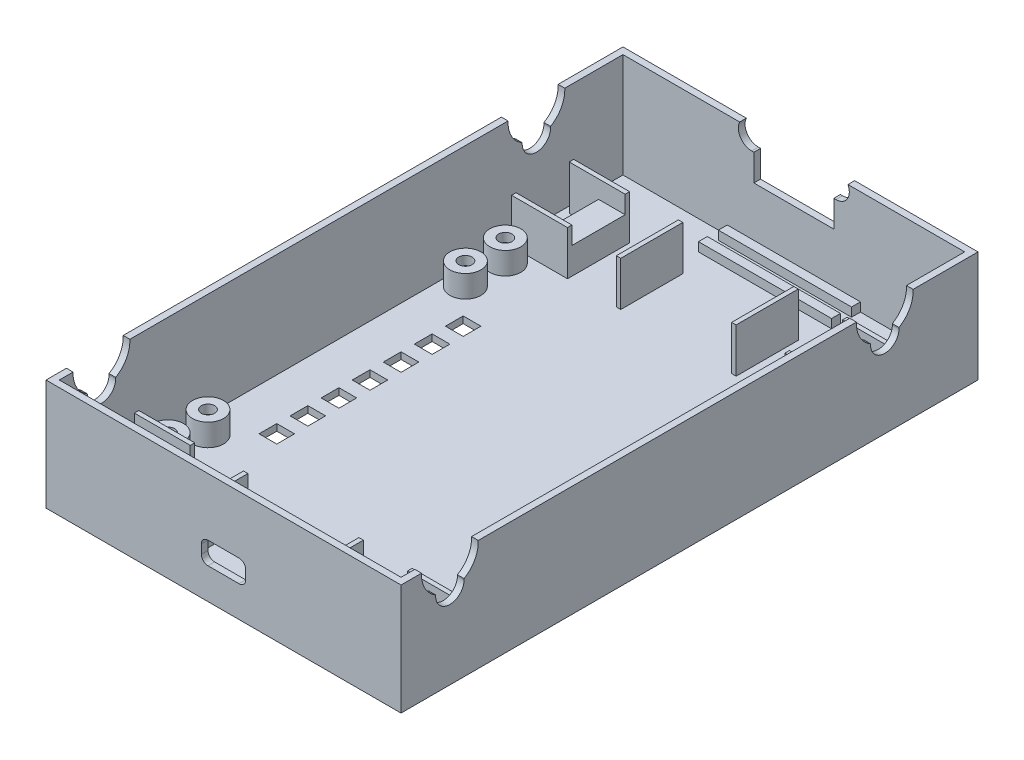
SolidWorks part; units mm, degrees
ref_plane "Спереди" through (0, 0, 0) normal (0, 0, 1) x (1, 0, 0)
ref_plane "Сверху" through (0, 0, 0) normal (0, 1, 0) x (1, 0, 0)
ref_plane "Справа" through (0, 0, 0) normal (1, 0, 0) x (0, 0, -1)
other "Configuration Table"
sketch "Корпус" plane through (0, 0, 0) normal (0, 1, 0) x (1, 0, 0)
  line L1 (40, -65) -> (-40, -65)
  line L2 (40, -65) -> (40, 65)
  line L3 (40, 65) -> (-40, 65)
  line L4 (-40, -65) -> (-40, 65)
  line L5 (40, -65) -> (-40, 65) construction
  line L6 (40, 65) -> (-40, -65) construction
  point P0 (0, 0)
  dimension "D1" = 80
  dimension "D2" = 130
sketch3d "Трехмерный эскиз1" plane through (0, 0, 0) normal (0, 0, 1) x (1, 0, 0)
extrude "Бобышка-Вытянуть1" add sketch "Корпус" along normal blind 25
sketch "Эскиз1" plane through (0, 25, 0) normal (0, 1, 0) x (1, 0, 0)
  line L0 (40, 65) -> (-40, 65) construction
  line L5 (-38.5, 63.5) -> (38.5, 63.5)
  line L6 (-38.5, 63.5) -> (-38.5, -63.5)
  line L7 (-38.5, -63.5) -> (38.5, -63.5)
  line L8 (38.5, 63.5) -> (38.5, -63.5)
  line L9 (-38.5, 63.5) -> (38.5, -63.5) construction
  line L10 (-38.5, -63.5) -> (38.5, 63.5) construction
  line L11 (-40, 65) -> (-40, -65) construction
  point P0 (0, 0)
  dimension "D1" = 1.5
  dimension "D2" = 1.5
extrude "Вырез-Вытянуть1" cut sketch "Эскиз1" against normal offset from surface (23.5 mm away) 1.5 up to face at (0, 0, 0)
sketch "Эскиз2" plane through (0, 0, -63.5) normal (0, 0, 1) x (1, 0, 0)
  line L0 (-14.3, 33.5) -> (14.3, 33.5) construction
  line L5 (-9, 26.7) -> (-9, 32.7)
  line L6 (-9, 32.7) -> (9, 32.7)
  line L7 (14.3, 33.5) -> (14.3, 4.5) construction
  line L8 (14.3, 4.5) -> (-14.3, 4.5) construction
  line L9 (-14.3, 4.5) -> (-14.3, 33.5) construction
  line L10 (0, 33.5) -> (0, 4.5) construction
  line L11 (9, 32.7) -> (9, 26.7)
  line L12 (9, 26.7) -> (9.5, 26.7)
  line L13 (-9, 26.7) -> (-9.5, 26.7)
  line L14 (9.5, 20.7) -> (9, 20.7)
  line L15 (9, 20.7) -> (9, 14.7)
  line L16 (9, 14.7) -> (-9, 14.7)
  line L17 (-9, 14.7) -> (-9, 20.7)
  line L18 (-9, 20.7) -> (-9.5, 20.7)
  line L20 (-12.5, 23.7) -> (12.5, 23.7) construction
  line L21 (-38.5, 1.5) -> (-38.5, 25) construction
  line L22 (38.5, 25) -> (-38.5, 25) construction
  line L23 (-40, 25) -> (40, 25) construction
  line L24 (0, 0) -> (0, 25) construction
  line L25 (-40, 0) -> (40, 0) construction
  arc A4 (-9.5, 26.7) -> (-9.5, 20.7) centre (-9.5, 23.7) ccw
  arc A5 (9.5, 26.7) -> (9.5, 20.7) centre (9.5, 23.7) cw
  point P32 (0, 23.7)
  dimension "D2" = 4.5
  dimension "D3" = 25
  dimension "D4" = 3
  dimension "D5" = 28.6
  dimension "D6" = 28.6
  dimension "D7" = 29
  dimension "D8" = 18
  dimension "D9" = 9.8
  dimension "D10" = 18
  dimension "D11" = 6
  dimension "D12" = 19.2
extrude "Вырез-Вытянуть2" cut sketch "Эскиз2" against normal blind 2
sketch "Эскиз3" plane through (-40, 0, 0) normal (-1, 0, 0) x (0, 0, 1)
  line L1 (-50, 34.7) -> (-38, 34.7) construction
  line L2 (-50, 34.7) -> (-50, 2.5) construction
  line L3 (-50, 2.5) -> (-38, 2.5) construction
  line L4 (-38, 34.7) -> (-38, 2.5) construction
  line L5 (-50, 34.7) -> (-38, 2.5) construction
  line L6 (-50, 2.5) -> (-38, 34.7) construction
  line L7 (-44, 34.7) -> (-44, 2.5) construction
  line L8 (-44, 28.9) -> (-44, 15.7) construction
  line L9 (-47.2, 18.9) -> (-47.2, 19.1574)
  line L10 (-65, 25) -> (-65, 0) construction
  line L12 (-65, 0) -> (65, 0) construction
  line L13 (-47.2, 18.9) -> (-47.2, 19.1574)
  line L14 (-40.8, 18.9) -> (-40.8, 19.1574)
  line L15 (-40.8, 18.9) -> (-40.8, 19.1574)
  line L16 (0, 0) -> (0, 25) construction
  line L17 (-65, 25) -> (65, 25) construction
  arc A1 (-47.2, 18.9) -> (-40.8, 18.9) centre (-44, 18.9) ccw
  arc A2 (-40.8, 19.1574) -> (-47.2, 19.1574) centre (-44, 24.7) ccw
  point P0 (-44, 18.6)
  dimension "D3" = 6.4
  dimension "D4" = 3.2
  dimension "D5" = 5.8
  dimension "D1" = 32.2
  dimension "D2" = 12
  dimension "D6" = 10
  dimension "D7" = 15
  dimension "D8" = 2.5
extrude "Вырез-Вытянуть3" cut sketch "Эскиз3" against normal blind 1.5 contours A1 L14 A2 L13
sketch "Эскиз5" plane through (-40, 0, 0) normal (-1, 0, 0) x (0, 0, 1)
  line L0 (0, 0) -> (0, 25) construction
  line L1 (-37.607, 25) -> (65, 25) construction
  line L2 (48, 34.7) -> (60, 34.7) construction
  line L3 (48, 34.7) -> (48, 2.5) construction
  line L6 (48, 2.5) -> (60, 2.5) construction
  line L8 (60, 34.7) -> (60, 2.5) construction
  line L9 (48, 34.7) -> (60, 2.5) construction
  line L10 (48, 2.5) -> (60, 34.7) construction
  line L11 (54, 34.7) -> (54, 2.5) construction
  line L12 (54, 28.9) -> (54, 15.7) construction
  line L13 (50.8, 18.9) -> (50.8, 19.1574)
  line L15 (50.8, 18.9) -> (50.8, 19.1574)
  line L16 (57.2, 18.9) -> (57.2, 19.1574)
  line L17 (57.2, 18.9) -> (57.2, 19.1574)
  line L18 (-65, 0) -> (65, 0) construction
  line L19 (65, 25) -> (65, 0) construction
  arc A0 (50.8, 18.9) -> (57.2, 18.9) centre (54, 18.9) ccw
  arc A1 (57.2, 19.1574) -> (50.8, 19.1574) centre (54, 24.7) ccw
  point P5 (54, 18.6)
  dimension "D1" = 32.2
  dimension "D2" = 12
  dimension "D5" = 6.4
  dimension "D6" = 3.2
  dimension "D4" = 10
  dimension "D7" = 5.8
  dimension "D8" = 2.5
  dimension "D9" = 5
extrude "Вырез-Вытянуть4" cut sketch "Эскиз5" against normal up to body from surface contours A1 L13 A0 L16 starting at face at (-40, 17.2019, -26.4)
sketch "Эскиз6" plane through (40, 0, 0) normal (1, 0, 0) x (0, 0, -1)
  line L0 (-60, 34.7) -> (-48, 34.7) construction
  line L1 (-60, 34.7) -> (-60, 2.5) construction
  line L2 (-60, 2.5) -> (-48, 2.5) construction
  line L3 (-48, 34.7) -> (-48, 2.5) construction
  line L4 (-60, 34.7) -> (-48, 2.5) construction
  line L5 (-60, 2.5) -> (-48, 34.7) construction
  line L6 (-54, 34.7) -> (-54, 2.5) construction
  line L7 (-54, 29.4) -> (-54, 15.7) construction
  line L8 (-57.2, 18.9) -> (-57.2, 19.1574)
  line L9 (-50.8, 18.9) -> (-50.8, 19.1574)
  line L12 (-65, 25) -> (-65, 0) construction
  line L13 (-65, 0) -> (65, 0) construction
  arc A0 (-57.2, 18.9) -> (-50.8, 18.9) centre (-54, 18.9) ccw
  arc A1 (-50.8, 19.1574) -> (-57.2, 19.1574) centre (-54, 24.7) ccw
  point P0 (-54, 18.6)
  dimension "D5" = 6.4
  dimension "D6" = 3.2
  dimension "D1" = 32.2
  dimension "D2" = 12
  dimension "D3" = 5.8
  dimension "D4" = 10
  dimension "D8" = 5
  dimension "D9" = 2.5
extrude "Вырез-Вытянуть5" cut sketch "Эскиз6" against normal up to surface (1.5 mm away) from surface up to face at (38.5, 13.25, 0) starting at face at (40, 12.5, 0)
sketch "Эскиз9" plane through (40, 0, 0) normal (1, 0, 0) x (0, 0, -1)
  line L0 (38, 34.7) -> (50, 34.7) construction
  line L1 (38, 34.7) -> (38, 2.5) construction
  line L2 (38, 2.5) -> (50, 2.5) construction
  line L3 (50, 34.7) -> (50, 2.5) construction
  line L4 (38, 34.7) -> (50, 2.5) construction
  line L5 (38, 2.5) -> (50, 34.7) construction
  line L6 (44, 34.7) -> (44, 2.5) construction
  line L7 (44, 28.9) -> (44, 15.7) construction
  line L8 (40.8, 18.9) -> (40.8, 19.1574)
  line L9 (40.8, 18.9) -> (40.8, 19.1574)
  line L10 (47.2, 18.9) -> (47.2, 19.1574)
  line L11 (47.2, 18.9) -> (47.2, 19.1574)
  line L12 (65, 25) -> (65, 0) construction
  line L13 (-65, 0) -> (65, 0) construction
  arc A0 (40.8, 18.9) -> (47.2, 18.9) centre (44, 18.9) ccw
  arc A1 (47.2, 19.1574) -> (40.8, 19.1574) centre (44, 24.7) ccw
  point P0 (44, 18.6)
  dimension "D5" = 6.4
  dimension "D6" = 3.2
  dimension "D1" = 32.2
  dimension "D2" = 12
  dimension "D3" = 5.8
  dimension "D4" = 10
  dimension "D8" = 15
  dimension "D9" = 2.5
extrude "Вырез-Вытянуть7" cut sketch "Эскиз9" against normal up to surface (1.5 mm away) from surface contours A1 L8 A0 L10 up to face at (38.5, 17.5019, 32.4) starting at face at (40, 17.2019, 32.4)
sketch "Эскиз10" plane through (0, 1.5, 0) normal (0, 1, 0) x (1, 0, 0)
  line L0 (-40, 44) -> (40, 44) construction
  line L3 (-40, -54) -> (40, -54) construction
  line L4 (-40, -50.8) -> (-40, -57.2) construction
  line L5 (40, -57.2) -> (40, -50.8) construction
  line L6 (-38.5, -63.5) -> (-38.5, 63.5) construction
  line L7 (-30.5, 38) -> (-24.5, 38)
  line L8 (-30.5, 38) -> (-30.5, 50)
  line L9 (-30.5, 50) -> (-24.5, 50)
  line L10 (-24.5, 38) -> (-24.5, 50)
  line L11 (-30.5, 38) -> (-24.5, 50) construction
  line L12 (-30.5, 50) -> (-24.5, 38) construction
  line L13 (24.5, 38) -> (30.5, 38)
  line L14 (24.5, 38) -> (24.5, 50)
  line L15 (24.5, 50) -> (30.5, 50)
  line L16 (30.5, 38) -> (30.5, 50)
  line L17 (24.5, 38) -> (30.5, 50) construction
  line L18 (24.5, 50) -> (30.5, 38) construction
  line L20 (-30.5, -60) -> (-24.5, -60)
  line L21 (-30.5, -60) -> (-30.5, -48)
  line L22 (-30.5, -48) -> (-24.5, -48)
  line L23 (-24.5, -60) -> (-24.5, -48)
  line L24 (-30.5, -60) -> (-24.5, -48) construction
  line L25 (-30.5, -48) -> (-24.5, -60) construction
  line L26 (24.5, -60) -> (30.5, -60)
  line L27 (24.5, -60) -> (24.5, -48)
  line L28 (24.5, -48) -> (30.5, -48)
  line L29 (30.5, -60) -> (30.5, -48)
  line L30 (24.5, -60) -> (30.5, -48) construction
  line L31 (24.5, -48) -> (30.5, -60) construction
  line L34 (-12.2037, 65) -> (-40, 65) construction
  line L35 (0, 65) -> (0, -65) construction
  line L36 (-9, 65) -> (9, 65) construction
  line L37 (-40, -65) -> (40, -65) construction
  line L38 (38.5, 63.5) -> (38.5, -63.5) construction
  point P4 (0, 44)
  point P12 (-27.5, 44)
  point P19 (27.5, 44)
  point P24 (30.5, 44)
  point P27 (-27.5, -54)
  point P32 (27.5, -54)
  point P37 (30.5, -54)
  point P38 (0, -54)
  point P46 (-30.5, -54)
  dimension "D1" = 12
  dimension "D2" = 98
  dimension "D3" = 6
  dimension "D4" = 6
  dimension "D5" = 12
  dimension "D6" = 8
  dimension "D7" = 12
  dimension "D8" = 6
  dimension "D9" = 6
  dimension "D10" = 12
  dimension "D11" = 8
  dimension "D12" = 8
  dimension "D13" = 21
  dimension "D14" = 8
extrude "Бобышка-Вытянуть2" add sketch "Эскиз10" along normal blind 6
sketch "Эскиз11" plane through (0, 1.5, 0) normal (0, 1, 0) x (1, 0, 0)
  line L0 (-24.5, 50) -> (-24.5, 51)
  line L1 (-24.5, 51) -> (-37.1, 51)
  line L2 (37.1, 50) -> (37.1, 51)
  line L3 (-24.5, 50) -> (-37.1, 50)
  line L4 (-37.1, 50) -> (-37.1, 51)
  line L5 (-24.5, 38) -> (-37.1, 38)
  line L6 (37.1, 51) -> (24.5, 51)
  line L7 (-37.1, 38) -> (-37.1, 37)
  line L8 (37.1, 50) -> (24.5, 50)
  line L9 (-37.1, 37) -> (-24.5, 37)
  line L10 (-24.5, 37) -> (-24.5, 38)
  line L11 (24.5, 50) -> (24.5, 51)
  line L12 (37.1, 38) -> (24.5, 38)
  line L13 (24.5, 38) -> (24.5, 37)
  line L14 (24.5, 37) -> (37.1, 37)
  line L15 (37.1, 37) -> (37.1, 38)
  line L16 (37.1, -48) -> (37.1, -47)
  line L17 (37.1, -47) -> (24.5, -47)
  line L18 (37.1, -48) -> (24.5, -48)
  line L19 (24.5, -48) -> (24.5, -47)
  line L20 (37.1, -60) -> (24.5, -60)
  line L21 (24.5, -60) -> (24.5, -61)
  line L22 (24.5, -61) -> (37.1, -61)
  line L23 (37.1, -61) -> (37.1, -60)
  line L24 (-24.5, -48) -> (-24.5, -47)
  line L25 (-24.5, -47) -> (-37.1, -47)
  line L26 (-24.5, -48) -> (-37.1, -48)
  line L27 (-37.1, -48) -> (-37.1, -47)
  line L28 (-24.5, -60) -> (-37.1, -60)
  line L29 (-37.1, -60) -> (-37.1, -61)
  line L30 (-37.1, -61) -> (-24.5, -61)
  line L31 (-24.5, -61) -> (-24.5, -60)
  dimension "D1" = 1
  dimension "D2" = 12.6
  dimension "D3" = 12.6
  dimension "D4" = 1
  dimension "D5" = 12.6
  dimension "D6" = 1
  dimension "D7" = 12.6
  dimension "D8" = 1
extrude "Бобышка-Вытянуть3" add sketch "Эскиз11" along normal blind 10
sketch "Эскиз13" plane through (0, 1.5, 0) normal (0, 1, 0) x (1, 0, 0)
  line L0 (-10, -63.5) -> (10, -63.5) construction
  line L1 (-40, -5) -> (40, -5) construction
  line L2 (10, -63.5) -> (10, -36.5) construction
  line L3 (10, -36.5) -> (37, -36.5) construction
  line L4 (37, -36.5) -> (37, 26.5) construction
  line L5 (37, 26.5) -> (-37, 26.5) construction
  line L6 (-40, -65) -> (40, -65) construction
  line L7 (-37, 26.5) -> (-37, -36.5) construction
  line L8 (-37, -36.5) -> (-10, -36.5) construction
  line L9 (-10, -36.5) -> (-10, -63.5) construction
  line L10 (-38.5, -63.5) -> (38.5, -63.5) construction
  line L11 (-40, 44) -> (-40, -54) construction
  line L12 (-40, 47.2) -> (-40, 40.8) construction
  line L14 (-40, -50.8) -> (-40, -57.2) construction
  circle A0 centre (-34.5, 24) radius 3.5
  circle A2 centre (34.5, 24) radius 3.5
  circle A3 centre (-34.5, -34) radius 3.5
  circle A4 centre (34.5, -34) radius 3.5
  circle A8 centre (-34.5, 33) radius 3.5
  circle A9 centre (34.5, 33) radius 3.5
  circle A10 centre (-34.5, -43) radius 3.5
  circle A11 centre (34.5, -43) radius 3.5
  circle A12 centre (0, -54) radius 3.5
  point P2 (0, -63.5)
  point P9 (0, -63.5)
  point P45 (-40, -5)
  dimension "D5" = 29
  dimension "D6" = 2.5
  dimension "D8" = 7
  dimension "D11" = 7
  dimension "D16" = 7
  dimension "D17" = 7
  dimension "D25" = 7
  dimension "D26" = 7
  dimension "D28" = 7
  dimension "D30" = 7
  dimension "D1" = 20
  dimension "D4" = 29
  dimension "D7" = 2.5
  dimension "D9" = 2.5
  dimension "D10" = 2.5
  dimension "D12" = 2.5
  dimension "D13" = 2.5
  dimension "D14" = 2.5
  dimension "D15" = 2.5
  dimension "D23" = 29
  dimension "D24" = 9
  dimension "D27" = 9
  dimension "D29" = 9
  dimension "D31" = 9
  dimension "D32" = 22
  dimension "D33" = 69
  dimension "D34" = 76
extrude "Бобышка-Вытянуть4" add sketch "Эскиз13" along normal blind 5
sketch "Эскиз14" plane through (0, 0, 0) normal (0, -1, 0) x (1, 0, 0)
  circle A2 centre (-34.5, 34) radius 2.5
  circle A3 centre (34.5, 34) radius 2.5
  circle A4 centre (-34.5, -24) radius 2.5
  circle A5 centre (34.5, -24) radius 2.5
  circle A6 centre (-34.5, -33) radius 2.5
  circle A7 centre (34.5, -33) radius 2.5
  circle A8 centre (34.5, 43) radius 2.5
  circle A9 centre (-34.5, 43) radius 2.5
  circle A10 centre (0, 54) radius 2.5
  dimension "D2" = 5
  dimension "D3" = 5
  dimension "D4" = 5
  dimension "D5" = 5
  dimension "D6" = 5
  dimension "D7" = 5
  dimension "D8" = 5
  dimension "D9" = 5
  dimension "D10" = 5
extrude "Вырез-Вытянуть8" cut sketch "Эскиз14" against normal offset from surface (4.5 mm away) 2 up to face at (-34.5, 6.5, -20.5)
sketch "Эскиз15" plane through (0, 6.5, 0) normal (0, 1, 0) x (1, 0, 0)
  circle A0 centre (-34.5, 24) radius 1.5
  circle A1 centre (34.5, 24) radius 1.5
  circle A2 centre (-34.5, -34) radius 1.5
  circle A3 centre (34.5, -34) radius 1.5
  circle A6 centre (-34.5, 33) radius 1.5
  circle A7 centre (34.5, 33) radius 1.5
  circle A9 centre (-34.5, -43) radius 1.5
  circle A11 centre (34.5, -43) radius 1.5
  circle A12 centre (0, -54) radius 1.5
  dimension "D1" = 3
  dimension "D2" = 3
  dimension "D3" = 3
  dimension "D4" = 3
  dimension "D5" = 3
  dimension "D7" = 3
  dimension "D8" = 3
  dimension "D9" = 3
  dimension "D10" = 3
extrude "Вырез-Вытянуть9" cut sketch "Эскиз15" against normal up to next
fillet "Скругление1" radius 1 9 edges at (34.5, 0, 31.5) (-34.5, 0, 31.5) (-34.5, 0, -26.5) (34.5, 0, -26.5) (34.5, 0, 40.5) (-34.5, 0, 40.5) (-34.5, 0, -35.5) (34.5, 0, -35.5) (0, 0, 51.5)
sketch "Эскиз16" plane through (0, 1.5, 0) normal (0, 1, 0) x (1, 0, 0)
  line L0 (-29, 11) -> (-25, 11)
  line L5 (-29, 18) -> (-25, 18)
  line L6 (-29, 18) -> (-29, 14)
  line L7 (-29, 14) -> (-25, 14)
  line L8 (-25, 18) -> (-25, 14)
  line L9 (-29, 18) -> (-25, 14) construction
  line L10 (-29, 14) -> (-25, 18) construction
  line L11 (-29, 11) -> (-29, 7)
  line L12 (-29, 7) -> (-25, 7)
  line L13 (-25, 11) -> (-25, 7)
  line L14 (-29, 11) -> (-25, 7) construction
  line L15 (-29, 7) -> (-25, 11) construction
  line L16 (0, 65) -> (0, -65) construction
  line L17 (-9, 65) -> (9, 65) construction
  line L18 (-40, -65) -> (40, -65) construction
  line L19 (-29, -3) -> (-25, -3)
  line L20 (-29, 4) -> (-25, 4)
  line L21 (-29, 4) -> (-29, 0)
  line L22 (-29, 0) -> (-25, 0)
  line L23 (-25, 4) -> (-25, 0)
  line L24 (-29, 4) -> (-25, 0) construction
  line L25 (-29, 0) -> (-25, 4) construction
  line L26 (-29, -3) -> (-29, -7)
  line L27 (-29, -7) -> (-25, -7)
  line L28 (-25, -3) -> (-25, -7)
  line L29 (-29, -3) -> (-25, -7) construction
  line L30 (-29, -7) -> (-25, -3) construction
  line L31 (-29, -17) -> (-25, -17)
  line L32 (-29, -10) -> (-25, -10)
  line L33 (-29, -10) -> (-29, -14)
  line L34 (-29, -14) -> (-25, -14)
  line L35 (-25, -10) -> (-25, -14)
  line L36 (-29, -10) -> (-25, -14) construction
  line L37 (-29, -14) -> (-25, -10) construction
  line L38 (-29, -17) -> (-29, -21)
  line L39 (-29, -21) -> (-25, -21)
  line L40 (-25, -17) -> (-25, -21)
  line L41 (-29, -17) -> (-25, -21) construction
  line L42 (-29, -21) -> (-25, -17) construction
  line L44 (-29, -24) -> (-25, -24)
  line L45 (-29, -24) -> (-29, -28)
  line L46 (-29, -28) -> (-25, -28)
  line L47 (-25, -24) -> (-25, -28)
  line L48 (-29, -24) -> (-25, -28) construction
  line L49 (-29, -28) -> (-25, -24) construction
  line L53 (-40, -5) -> (40, -5) construction
  line L56 (29, -28) -> (25, -24) construction
  line L57 (29, -24) -> (25, -28) construction
  line L58 (29, -21) -> (25, -17) construction
  line L59 (29, -17) -> (25, -21) construction
  line L60 (29, -14) -> (25, -10) construction
  line L61 (29, -10) -> (25, -14) construction
  line L62 (29, -7) -> (25, -3) construction
  line L63 (29, -3) -> (25, -7) construction
  line L64 (29, 0) -> (25, 4) construction
  line L65 (29, 4) -> (25, 0) construction
  line L66 (29, 7) -> (25, 11) construction
  line L67 (29, 11) -> (25, 7) construction
  line L68 (29, 14) -> (25, 18) construction
  line L69 (29, 18) -> (25, 14) construction
  line L70 (25, -24) -> (25, -28)
  line L71 (29, -28) -> (25, -28)
  line L72 (29, -24) -> (29, -28)
  line L73 (29, -24) -> (25, -24)
  line L74 (25, -17) -> (25, -21)
  line L75 (29, -21) -> (25, -21)
  line L76 (29, -17) -> (29, -21)
  line L77 (25, -10) -> (25, -14)
  line L78 (29, -14) -> (25, -14)
  line L79 (29, -10) -> (29, -14)
  line L80 (29, -10) -> (25, -10)
  line L81 (29, -17) -> (25, -17)
  line L82 (25, -3) -> (25, -7)
  line L83 (29, -7) -> (25, -7)
  line L84 (29, -3) -> (29, -7)
  line L85 (25, 4) -> (25, 0)
  line L86 (29, 0) -> (25, 0)
  line L87 (29, 4) -> (29, 0)
  line L88 (29, 4) -> (25, 4)
  line L89 (29, -3) -> (25, -3)
  line L90 (25, 11) -> (25, 7)
  line L91 (29, 7) -> (25, 7)
  line L92 (29, 11) -> (29, 7)
  line L93 (25, 18) -> (25, 14)
  line L94 (29, 14) -> (25, 14)
  line L95 (29, 18) -> (29, 14)
  line L96 (29, 18) -> (25, 18)
  line L97 (29, 11) -> (25, 11)
  point P0 (-27, 16)
  point P5 (-27, 9)
  point P10 (-27, 2)
  point P21 (-27, -5)
  point P26 (-27, -12)
  point P31 (-27, -19)
  point P36 (-27, -26)
  point P76 (27, -26)
  point P77 (27, -19)
  point P78 (27, -12)
  point P79 (27, -5)
  point P80 (27, 2)
  point P81 (27, 9)
  point P82 (27, 16)
  dimension "D1" = 4
  dimension "D2" = 4
  dimension "D3" = 4
  dimension "D4" = 3
  dimension "D5" = 4
  dimension "D6" = 25
  dimension "D7" = 25
  dimension "D8" = 4
  dimension "D9" = 4
  dimension "D10" = 4
  dimension "D11" = 3
  dimension "D12" = 4
  dimension "D13" = 4
  dimension "D14" = 4
  dimension "D15" = 4
  dimension "D16" = 3
  dimension "D17" = 4
  dimension "D18" = 4
  dimension "D22" = 25
  dimension "D23" = 25
  dimension "D24" = 25
  dimension "D25" = 25
  dimension "D26" = 25
  dimension "D28" = 3
  dimension "D29" = 3
  dimension "D30" = 3
  dimension "D31" = 4
extrude "Вырез-Вытянуть10" cut sketch "Эскиз16" against normal up to next
sketch "Эскиз17" plane through (0, 0, 65) normal (0, 0, 1) x (1, 0, 0)
  line L0 (0, 25) -> (0, 0) construction
  line L1 (-40, 25) -> (40, 25) construction
  line L16 (-40, 0) -> (40, 0) construction
  line L17 (-3.5, 12) -> (3.5, 12)
  line L18 (-5, 10.5) -> (-5, 8.5)
  line L19 (-3.5, 7) -> (3.5, 7)
  line L20 (5, 10.5) -> (5, 8.5)
  arc A6 (-5, 10.5) -> (-3.5, 12) centre (-3.5, 10.5) cw
  arc A7 (3.5, 12) -> (5, 10.5) centre (3.5, 10.5) cw
  arc A8 (-3.5, 7) -> (-5, 8.5) centre (-3.5, 8.5) cw
  arc A9 (5, 8.5) -> (3.5, 7) centre (3.5, 8.5) cw
  point P5 (0, 9.5)
  dimension "D4" = 1.5
  dimension "D1" = 10
  dimension "D2" = 5
  dimension "D3" = 7
extrude "Вырез-Вытянуть12" cut sketch "Эскиз17" against normal up to surface (1.5 mm away) up to face at (0, 13.25, 63.5)
sketch "Эскиз18" plane through (0, 1.5, 0) normal (0, 1, 0) x (1, 0, 0)
  line L0 (0, 65) -> (0, -65) construction
  line L1 (-15, 63.5) -> (15, 63.5)
  line L2 (-15, 63.5) -> (-15, 61.5)
  line L3 (-15, 61.5) -> (15, 61.5)
  line L4 (15, 63.5) -> (15, 61.5)
  line L5 (-15, 63.5) -> (15, 61.5) construction
  line L6 (-15, 61.5) -> (15, 63.5) construction
  line L7 (-9, 65) -> (9, 65) construction
  line L8 (-40, -65) -> (40, -65) construction
  line L9 (-38.5, 63.5) -> (38.5, 63.5) construction
  line L11 (-15, 59) -> (15, 59)
  line L12 (-15, 59) -> (-15, 57)
  line L13 (-15, 57) -> (15, 57)
  line L14 (15, 59) -> (15, 57)
  line L15 (-15, 59) -> (15, 57) construction
  line L16 (-15, 57) -> (15, 59) construction
  point P0 (0, 62.5)
  point P11 (0, 63.5)
  point P14 (0, 58)
  dimension "D1" = 2
  dimension "D2" = 30
  dimension "D3" = 2
  dimension "D4" = 2.5
extrude "Бобышка-Вытянуть5" add sketch "Эскиз18" along normal blind 2
sketch "Эскиз19" plane through (0, 1.5, 0) normal (0, 1, 0) x (1, 0, 0)
  line L0 (-40, 44) -> (40, 44) construction
  line L1 (-13.5, 51) -> (-12.5, 51)
  line L2 (-13.5, 51) -> (-13.5, 37)
  line L3 (-13.5, 37) -> (-12.5, 37)
  line L4 (-12.5, 51) -> (-12.5, 37)
  line L5 (-13.5, 51) -> (-12.5, 37) construction
  line L6 (-13.5, 37) -> (-12.5, 51) construction
  line L7 (40, 40.8) -> (40, 47.2) construction
  line L8 (-38.5, -63.5) -> (-38.5, 63.5) construction
  line L9 (12.5, 51) -> (13.5, 51)
  line L10 (12.5, 51) -> (12.5, 37)
  line L11 (12.5, 37) -> (13.5, 37)
  line L12 (13.5, 51) -> (13.5, 37)
  line L13 (12.5, 51) -> (13.5, 37) construction
  line L14 (12.5, 37) -> (13.5, 51) construction
  line L15 (38.5, 50.393) -> (38.5, 63.5) construction
  line L16 (-40, -54) -> (40, -54) construction
  line L17 (40, -57.2) -> (40, -50.8) construction
  line L18 (-13.5, -47) -> (-12.5, -47)
  line L19 (-13.5, -47) -> (-13.5, -61)
  line L20 (-13.5, -61) -> (-12.5, -61)
  line L21 (-12.5, -47) -> (-12.5, -61)
  line L22 (-13.5, -47) -> (-12.5, -61) construction
  line L23 (-13.5, -61) -> (-12.5, -47) construction
  line L24 (12.5, -47) -> (13.5, -47)
  line L25 (12.5, -47) -> (12.5, -61)
  line L26 (12.5, -61) -> (13.5, -61)
  line L27 (13.5, -47) -> (13.5, -61)
  line L28 (12.5, -47) -> (13.5, -61) construction
  line L29 (12.5, -61) -> (13.5, -47) construction
  line L30 (38.5, -47.607) -> (38.5, 37.607) construction
  point P0 (-13, 44)
  point P13 (13, 44)
  point P24 (-13, -54)
  point P29 (13, -54)
  dimension "D1" = 14
  dimension "D2" = 1
  dimension "D3" = 25
  dimension "D4" = 14
  dimension "D5" = 1
  dimension "D6" = 25
  dimension "D7" = 14
  dimension "D8" = 1
  dimension "D9" = 14
  dimension "D10" = 1
  dimension "D11" = 25
  dimension "D12" = 25
extrude "Бобышка-Вытянуть6" add sketch "Эскиз19" along normal blind 10
